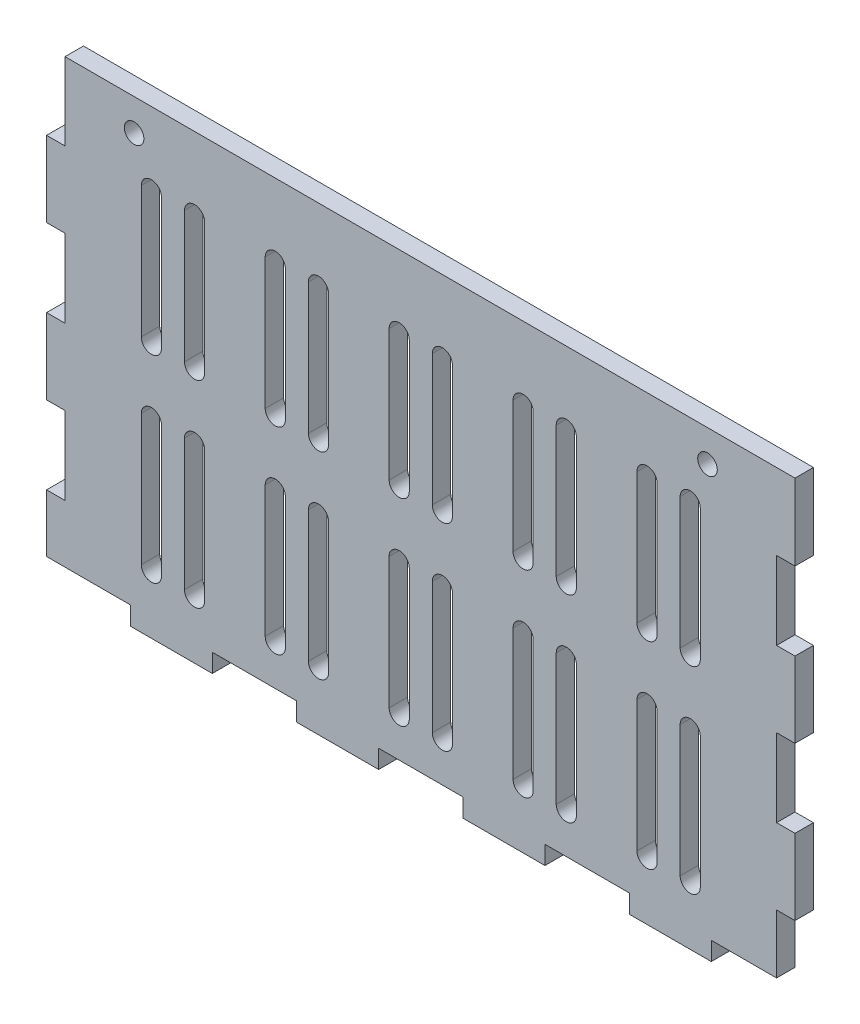
SolidWorks part; units mm, degrees
material "Acrylic (Medium-high impact)"
ref_plane "Front Plane" through (0, 0, 0) normal (0, 0, 1) x (1, 0, 0)
ref_plane "Top Plane" through (0, 0, 0) normal (0, 1, 0) x (1, 0, 0)
ref_plane "Right Plane" through (0, 0, 0) normal (1, 0, 0) x (0, 0, -1)
sketch "Sketch1" plane through (0, 0, 0) normal (0, 0, 1) x (1, 0, 0)
  line L1 (0, 0) -> (130, 0)
  line L2 (0, 0) -> (0, 80)
  line L3 (0, 80) -> (130, 80)
  line L4 (130, 0) -> (130, 80)
  dimension "D1" = 130
  dimension "D2" = 80
extrude "Boss-Extrude1" add sketch "Sketch1" along normal blind 3.2
sketch "Sketch2" plane through (0, 0, 3.2) normal (0, 0, 1) x (1, 0, 0)
  line L61 (14.4444, 3.2) -> (28.8889, 3.2) construction
  line L62 (0, 0) -> (14.4444, 0)
  line L67 (0, 0) -> (0, 3.2)
  line L72 (0, 3.2) -> (14.4444, 3.2)
  line L77 (14.4444, 0) -> (14.4444, 3.2)
  line L97 (28.8889, 0) -> (28.8889, 3.2)
  line L98 (28.8889, 0) -> (43.3333, 0)
  line L107 (43.3333, 0) -> (43.3333, 3.2)
  line L115 (28.8889, 3.2) -> (43.3333, 3.2)
  line L117 (43.3333, 3.2) -> (57.7778, 3.2) construction
  line L123 (57.7778, 0) -> (57.7778, 3.2)
  line L128 (57.7778, 0) -> (72.2222, 0)
  line L129 (72.2222, 0) -> (72.2222, 3.2)
  line L131 (57.7778, 3.2) -> (72.2222, 3.2)
  line L132 (72.2222, 3.2) -> (86.6667, 3.2) construction
  line L133 (86.6667, 0) -> (86.6667, 3.2)
  line L134 (86.6667, 0) -> (101.1111, 0)
  line L135 (101.1111, 0) -> (101.1111, 3.2)
  line L136 (86.6667, 3.2) -> (101.1111, 3.2)
  line L137 (101.1111, 3.2) -> (115.5556, 3.2) construction
  line L138 (115.5556, 0) -> (115.5556, 3.2)
  line L139 (115.5556, 0) -> (130, 0)
  line L142 (130, 0) -> (130, 80) construction
  line L143 (0, 80) -> (0, 0) construction
  line L144 (0, 13.3333) -> (3.2, 13.3333)
  line L145 (0, 13.3333) -> (0, 26.6667)
  line L146 (130, 3.2) -> (144.4444, 3.2) construction
  line L147 (0, 26.6667) -> (3.2, 26.6667)
  line L148 (3.2, 13.3333) -> (3.2, 26.6667)
  line L149 (3.2, 13.3333) -> (3.2, 0) construction
  line L150 (0, 40) -> (0, 53.3333)
  line L151 (0, 40) -> (3.2, 40)
  line L152 (3.2, 40) -> (3.2, 53.3333)
  line L153 (0, 53.3333) -> (3.2, 53.3333)
  line L154 (3.2, 40) -> (3.2, 26.6667) construction
  line L155 (0, 66.6667) -> (0, 80)
  line L156 (0, 66.6667) -> (3.2, 66.6667)
  line L157 (3.2, 66.6667) -> (3.2, 80)
  line L158 (0, 80) -> (3.2, 80)
  line L159 (3.2, 66.6667) -> (3.2, 53.3333) construction
  line L160 (130, 80) -> (0, 80) construction
  line L161 (126.8, 80) -> (126.8, 66.6667) construction
  line L162 (126.8, 40) -> (126.8, 26.6667)
  line L163 (126.8, 66.6667) -> (130, 66.6667)
  line L164 (126.8, 66.6667) -> (126.8, 53.3333)
  line L165 (126.8, 53.3333) -> (130, 53.3333)
  line L166 (130, 66.6667) -> (130, 53.3333)
  line L167 (126.8, 40) -> (130, 40)
  line L168 (130, 40) -> (130, 26.6667)
  line L169 (126.8, 26.6667) -> (130, 26.6667)
  line L170 (126.8, 53.3333) -> (126.8, 40) construction
  line L172 (126.8, 13.3333) -> (130, 13.3333)
  line L173 (130, 13.3333) -> (130, 0)
  line L175 (126.8, 26.6667) -> (126.8, 13.3333) construction
  line L183 (115.5556, 3.2) -> (130, 3.2) [skipped]
  line L184 (130, 0) -> (130, 3.2) [skipped]
  line L185 (126.8, 13.3333) -> (126.8, 3.2)
  line L186 (126.8, 3.2) -> (115.5556, 3.2)
  line L187 (126.8, 0) -> (130, 0) [skipped]
  line L188 (126.8, 13.3333) -> (126.8, 0) [skipped]
  dimension "D2" = 3.2
  dimension "D4" = 3.2
  dimension "D6" = 3.2
  dimension "D1" = 5
  dimension "D3" = 3
  dimension "D5" = 3
extrude "Cut-Extrude1" cut sketch "Sketch2" against normal through all
sketch "Sketch3" plane through (0, 0, 3.2) normal (0, 0, 1) x (1, 0, 0)
  line L0 (0, 66.6667) -> (0, 53.3333) construction
  line L1 (130, 80) -> (3.2, 80) construction
  line L2 (0, 66.6667) -> (130, 66.6667) construction
  line L3 (65, 66.6667) -> (65, 50066.6667) construction
  circle A0 centre (15.2, 74.5) radius 1.7
  circle A1 centre (114.8, 74.5) radius 1.7
  point P10 (65, 66.6667)
  dimension "D1" = 3.4
  dimension "D2" = 15.2
  dimension "D3" = 5.5
extrude "Cut-Extrude2" cut sketch "Sketch3" against normal up to next
sketch "Sketch4" plane through (0, 0, 3.2) normal (0, 0, 1) x (1, 0, 0)
  line L0 (18.2, 10.2) -> (18.2, 32.975) construction
  line L1 (16.45, 10.2) -> (16.45, 32.975)
  line L2 (19.95, 10.2) -> (19.95, 32.975)
  line L3 (18.2, 44.475) -> (18.2, 67.25) construction
  line L4 (16.45, 44.475) -> (16.45, 67.25)
  line L5 (19.95, 44.475) -> (19.95, 67.25)
  line L6 (25.7, 10.2) -> (25.7, 32.975) construction
  line L7 (23.95, 10.2) -> (23.95, 32.975)
  line L8 (27.45, 10.2) -> (27.45, 32.975)
  line L9 (25.7, 44.475) -> (25.7, 67.25) construction
  line L10 (23.95, 44.475) -> (23.95, 67.25)
  line L11 (27.45, 44.475) -> (27.45, 67.25)
  line L13 (130, 80) -> (3.2, 80) construction
  line L14 (14.4444, 3.2) -> (0, 3.2) construction
  line L15 (41.475, 10.2) -> (41.475, 32.975)
  line L17 (37.975, 10.2) -> (37.975, 32.975)
  line L18 (48.975, 10.2) -> (48.975, 32.975)
  line L19 (45.475, 10.2) -> (45.475, 32.975)
  line L20 (48.975, 44.475) -> (48.975, 67.25)
  line L21 (45.475, 44.475) -> (45.475, 67.25)
  line L22 (41.475, 44.475) -> (41.475, 67.25)
  line L23 (37.975, 44.475) -> (37.975, 67.25)
  line L24 (39.725, 10.2) -> (39.725, 32.975) construction
  line L25 (39.725, 44.475) -> (39.725, 67.25) construction
  line L26 (47.225, 10.2) -> (47.225, 32.975) construction
  line L27 (47.225, 44.475) -> (47.225, 67.25) construction
  line L28 (63, 10.2) -> (63, 32.975)
  line L29 (59.5, 10.2) -> (59.5, 32.975)
  line L30 (70.5, 10.2) -> (70.5, 32.975)
  line L31 (67, 10.2) -> (67, 32.975)
  line L32 (70.5, 44.475) -> (70.5, 67.25)
  line L33 (67, 44.475) -> (67, 67.25)
  line L34 (63, 44.475) -> (63, 67.25)
  line L35 (59.5, 44.475) -> (59.5, 67.25)
  line L36 (61.25, 10.2) -> (61.25, 32.975) construction
  line L37 (61.25, 44.475) -> (61.25, 67.25) construction
  line L38 (68.75, 10.2) -> (68.75, 32.975) construction
  line L39 (68.75, 44.475) -> (68.75, 67.25) construction
  line L40 (84.525, 10.2) -> (84.525, 32.975)
  line L41 (81.025, 10.2) -> (81.025, 32.975)
  line L42 (92.025, 10.2) -> (92.025, 32.975)
  line L43 (88.525, 10.2) -> (88.525, 32.975)
  line L44 (92.025, 44.475) -> (92.025, 67.25)
  line L45 (88.525, 44.475) -> (88.525, 67.25)
  line L46 (84.525, 44.475) -> (84.525, 67.25)
  line L47 (81.025, 44.475) -> (81.025, 67.25)
  line L48 (82.775, 10.2) -> (82.775, 32.975) construction
  line L49 (82.775, 44.475) -> (82.775, 67.25) construction
  line L50 (90.275, 10.2) -> (90.275, 32.975) construction
  line L51 (90.275, 44.475) -> (90.275, 67.25) construction
  line L52 (106.05, 10.2) -> (106.05, 32.975)
  line L53 (102.55, 10.2) -> (102.55, 32.975)
  line L54 (113.55, 10.2) -> (113.55, 32.975)
  line L55 (110.05, 10.2) -> (110.05, 32.975)
  line L56 (113.55, 44.475) -> (113.55, 67.25)
  line L57 (110.05, 44.475) -> (110.05, 67.25)
  line L58 (106.05, 44.475) -> (106.05, 67.25)
  line L59 (102.55, 44.475) -> (102.55, 67.25)
  line L60 (104.3, 10.2) -> (104.3, 32.975) construction
  line L61 (104.3, 44.475) -> (104.3, 67.25) construction
  line L62 (111.8, 10.2) -> (111.8, 32.975) construction
  line L63 (111.8, 44.475) -> (111.8, 67.25) construction
  line L64 (18.2, 21.5875) -> (3.2, 21.5875) construction
  line L65 (3.2, 13.3333) -> (3.2, 26.6667) construction
  line L66 (111.8, 21.5875) -> (126.8, 21.5875) construction
  line L67 (126.8, 26.6667) -> (126.8, 13.3333) construction
  line L68 (18.2, 32.975) -> (25.7, 32.975) construction
  arc A0 (16.45, 10.2) -> (19.95, 10.2) centre (18.2, 10.2) ccw
  arc A1 (19.95, 32.975) -> (16.45, 32.975) centre (18.2, 32.975) ccw
  arc A2 (16.45, 44.475) -> (19.95, 44.475) centre (18.2, 44.475) ccw
  arc A3 (19.95, 67.25) -> (16.45, 67.25) centre (18.2, 67.25) ccw
  arc A4 (23.95, 10.2) -> (27.45, 10.2) centre (25.7, 10.2) ccw
  arc A5 (27.45, 32.975) -> (23.95, 32.975) centre (25.7, 32.975) ccw
  arc A6 (23.95, 44.475) -> (27.45, 44.475) centre (25.7, 44.475) ccw
  arc A7 (27.45, 67.25) -> (23.95, 67.25) centre (25.7, 67.25) ccw
  arc A8 (37.975, 10.2) -> (41.475, 10.2) centre (39.725, 10.2) ccw
  arc A9 (41.475, 32.975) -> (37.975, 32.975) centre (39.725, 32.975) ccw
  arc A10 (45.475, 10.2) -> (48.975, 10.2) centre (47.225, 10.2) ccw
  arc A11 (48.975, 32.975) -> (45.475, 32.975) centre (47.225, 32.975) ccw
  arc A12 (45.475, 44.475) -> (48.975, 44.475) centre (47.225, 44.475) ccw
  arc A13 (48.975, 67.25) -> (45.475, 67.25) centre (47.225, 67.25) ccw
  arc A14 (37.975, 44.475) -> (41.475, 44.475) centre (39.725, 44.475) ccw
  arc A15 (41.475, 67.25) -> (37.975, 67.25) centre (39.725, 67.25) ccw
  arc A16 (59.5, 10.2) -> (63, 10.2) centre (61.25, 10.2) ccw
  arc A17 (63, 32.975) -> (59.5, 32.975) centre (61.25, 32.975) ccw
  arc A18 (67, 10.2) -> (70.5, 10.2) centre (68.75, 10.2) ccw
  arc A19 (70.5, 32.975) -> (67, 32.975) centre (68.75, 32.975) ccw
  arc A20 (67, 44.475) -> (70.5, 44.475) centre (68.75, 44.475) ccw
  arc A21 (70.5, 67.25) -> (67, 67.25) centre (68.75, 67.25) ccw
  arc A22 (59.5, 44.475) -> (63, 44.475) centre (61.25, 44.475) ccw
  arc A23 (63, 67.25) -> (59.5, 67.25) centre (61.25, 67.25) ccw
  arc A24 (81.025, 10.2) -> (84.525, 10.2) centre (82.775, 10.2) ccw
  arc A25 (84.525, 32.975) -> (81.025, 32.975) centre (82.775, 32.975) ccw
  arc A26 (88.525, 10.2) -> (92.025, 10.2) centre (90.275, 10.2) ccw
  arc A27 (92.025, 32.975) -> (88.525, 32.975) centre (90.275, 32.975) ccw
  arc A28 (88.525, 44.475) -> (92.025, 44.475) centre (90.275, 44.475) ccw
  arc A29 (92.025, 67.25) -> (88.525, 67.25) centre (90.275, 67.25) ccw
  arc A30 (81.025, 44.475) -> (84.525, 44.475) centre (82.775, 44.475) ccw
  arc A31 (84.525, 67.25) -> (81.025, 67.25) centre (82.775, 67.25) ccw
  arc A32 (102.55, 10.2) -> (106.05, 10.2) centre (104.3, 10.2) ccw
  arc A33 (106.05, 32.975) -> (102.55, 32.975) centre (104.3, 32.975) ccw
  arc A34 (110.05, 10.2) -> (113.55, 10.2) centre (111.8, 10.2) ccw
  arc A35 (113.55, 32.975) -> (110.05, 32.975) centre (111.8, 32.975) ccw
  arc A36 (110.05, 44.475) -> (113.55, 44.475) centre (111.8, 44.475) ccw
  arc A37 (113.55, 67.25) -> (110.05, 67.25) centre (111.8, 67.25) ccw
  arc A38 (102.55, 44.475) -> (106.05, 44.475) centre (104.3, 44.475) ccw
  arc A39 (106.05, 67.25) -> (102.55, 67.25) centre (104.3, 67.25) ccw
  point P2 (18.2, 21.5875)
  point P7 (18.2, 55.8625)
  point P14 (25.7, 21.5875)
  point P21 (25.7, 55.8625)
  point P36 (39.725, 21.5875)
  point P41 (39.725, 55.8625)
  point P48 (47.225, 21.5875)
  point P55 (47.225, 55.8625)
  point P64 (61.25, 21.5875)
  point P69 (61.25, 55.8625)
  point P76 (68.75, 21.5875)
  point P83 (68.75, 55.8625)
  point P92 (82.775, 21.5875)
  point P97 (82.775, 55.8625)
  point P104 (90.275, 21.5875)
  point P111 (90.275, 55.8625)
  point P120 (104.3, 21.5875)
  point P125 (104.3, 55.8625)
  point P132 (111.8, 21.5875)
  point P139 (111.8, 55.8625)
  dimension "D3" = 11
  dimension "D5" = 8
  dimension "D1" = 3.5
  dimension "D2" = 4
  dimension "D4" = 7
  dimension "D7" = 15
  dimension "D6" = 5
extrude "Cut-Extrude3" cut sketch "Sketch4" against normal up to next
other "Width tolerance" flip direction yes face at (128.4, 53.3333, 1.6) face at (128.4, 26.6667, 1.6) face at (128.4, 13.3333, 1.6) face at (128.4, 40, 1.6) face at (128.4, 66.6667, 1.6) face at (115.5556, 1.6, 1.6) face at (86.6667, 1.6, 1.6) face at (57.7778, 1.6, 1.6) face at (28.8889, 1.6, 1.6) face at (14.4444, 1.6, 1.6) face at (43.3333, 1.6, 1.6) face at (72.2222, 1.6, 1.6) face at (101.1111, 1.6, 1.6) face at (1.6, 26.6667, 1.6) face at (1.6, 13.3333, 1.6) face at (1.6, 40, 1.6) face at (1.6, 53.3333, 1.6) face at (1.6, 66.6667, 1.6) offset 0.1 parameters "D1"=0.1
equation "\"wall_thickness\"= 3.2mm"
equation "\"D1@Boss-Extrude1\"=\"wall_thickness\""
equation "\"slot_width_tolerance\"= 0.1mm"
equation "\"slot_depth\"= 3.2mm"
equation "\"D2@Sketch2\"=\"slot_depth\""
equation "\"D4@Sketch2\"=\"slot_depth\""
equation "\"D6@Sketch2\"=\"slot_depth\""
equation "\"D2@Sketch3\"=12.00mm+\"slot_depth\""
equation "\"D1@Width tolerance\"=\"slot_width_tolerance\""
